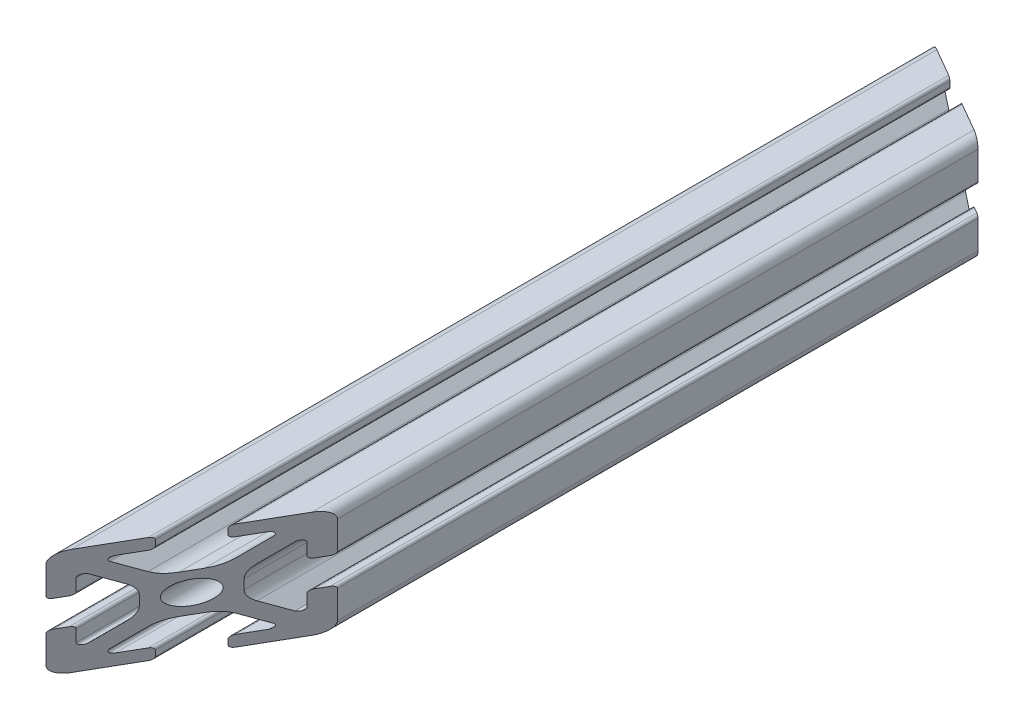
SolidWorks part; units mm, degrees
ref_plane "Front Plane" through (0, 0, 0) normal (0, 0, 1) x (1, 0, 0)
ref_plane "Top Plane" through (0, 0, 0) normal (0, 1, 0) x (1, 0, 0)
ref_plane "Right Plane" through (0, 0, 0) normal (1, 0, 0) x (0, 0, -1)
sketch "Sketch2" plane through (0, 0, 0) normal (0, 0, 1) x (1, 0, 0)
  line L0 (0, 10) -> (0, -10) construction
  line L1 (-10, 0) -> (10, 0) construction
  line L2 (2.5, -10) -> (10, -10)
  line L3 (10, -10) -> (10, -2.5)
  line L4 (2.5, -10) -> (2.5, -7.9246)
  line L5 (2.5, -7.9246) -> (6.4571, -7.9246)
  line L6 (6.4571, -7.9246) -> (2.1325, -3.6)
  line L7 (0, 0) -> (10, -10) construction
  line L8 (10, -2.5) -> (7.9246, -2.5)
  line L9 (7.9246, -2.5) -> (7.9246, -6.4571)
  line L10 (7.9246, -6.4571) -> (3.6, -2.1325)
  line L11 (5.7623, -4.2948) -> (4.2948, -5.7623) construction
  circle A0 centre (0, 0) radius 2.15
  arc A1 (5.25, -7.9246) -> (5.6036, -7.0711) centre (5.25, -7.4246) ccw construction
  point P8 (0, -3.6)
  point P16 (5.0286, -5.0286)
  dimension "Center Hole Diameter" = 4.3
  dimension "D3" = 0.5
  dimension "Rail Height" = 20
  dimension "Rail Width" = 20
  dimension "T-Slot Width" = 5
  dimension "Slot Depth" = 6.4
  dimension "Slot Inner Width" = 11.5
sketch "Sketch3" plane through (0, 0, 0) normal (1, 0, 0) x (0, 0, -1)
  line L0 (-100, -10) -> (100, -10) construction
  line L1 (-74.6, 0) -> (74.6, 0) construction
  line L2 (0, 10) -> (0, -10) construction
  line L3 (0, 10) -> (0, -10) construction
  point P6 (-74.6, 0)
  point P8 (74.6, 0)
  dimension "Length" = 200
  dimension "D1" = 25.4
sketch "Sketch4" plane through (0, 0, 0) normal (0, 0, 1) x (1, 0, 0)
  line L0 (3, -10) -> (8.25, -10)
  line L1 (2.5, -10) -> (10, -10) construction
  line L2 (2.5, -10) -> (2.5, -7.9246) construction
  line L3 (2.5, -7.9246) -> (6.4571, -7.9246) construction
  line L4 (2.5, -8.4246) -> (2.5, -9.5)
  line L5 (3, -7.9246) -> (5.25, -7.9246)
  line L6 (0, -3.6) -> (0.8898, -3.6)
  line L7 (6.4571, -7.9246) -> (2.1325, -3.6) construction
  line L8 (3.0112, -4.4787) -> (5.6036, -7.0711)
  line L9 (10, -10) -> (10, -2.5) construction
  line L10 (7.9246, -6.4571) -> (3.6, -2.1325) construction
  line L11 (7.9246, -2.5) -> (7.9246, -6.4571) construction
  line L12 (7.9246, -5.25) -> (7.9246, -3)
  line L13 (10, -2.5) -> (7.9246, -2.5) construction
  line L14 (8.4246, -2.5) -> (9.5, -2.5)
  line L15 (10, -3) -> (10, -8.25)
  line L16 (7.0711, -5.6036) -> (4.4787, -3.0112)
  line L17 (3.6, 0) -> (3.6, -0.8898)
  line L18 (-10, 0) -> (10, 0) construction
  line L19 (0, -3.6) -> (0, -2.15)
  line L20 (0, 10) -> (0, -10) construction
  line L21 (3.6, 0) -> (2.15, 0)
  arc A0 (2.5, -9.5) -> (3, -10) centre (3, -9.5) ccw
  arc A1 (5.25, -7.9246) -> (5.6036, -7.0711) centre (5.25, -7.4246) ccw construction
  arc A2 (2.5, -8.4246) -> (3, -7.9246) centre (3, -8.4246) cw
  arc A3 (5.25, -7.9246) -> (5.6036, -7.0711) centre (5.25, -7.4246) ccw
  arc A4 (0.8898, -3.6) -> (3.0112, -4.4787) centre (0.8898, -6.6) cw
  arc A5 (8.25, -10) -> (10, -8.25) centre (8.25, -8.25) ccw
  arc A6 (7.0711, -5.6036) -> (7.9246, -5.25) centre (7.4246, -5.25) ccw
  arc A7 (7.9246, -3) -> (8.4246, -2.5) centre (8.4246, -3) cw
  arc A8 (9.5, -2.5) -> (10, -3) centre (9.5, -3) cw
  arc A9 (4.4787, -3.0112) -> (3.6, -0.8898) centre (6.6, -0.8898) cw
  circle A10 centre (0, 0) radius 2.15 construction
  arc A11 (0, -2.15) -> (2.15, 0) centre (0, 0) ccw
  dimension "D1" = 1.75
  dimension "D2" = 3
extrude "Boss-Extrude1" add sketch "Sketch4" along normal mid plane 200
mirror "Mirror1" about plane through (0, 0, 0) normal (1, 0, 0) of bodies 134
mirror "Mirror2" about plane through (0, 0, 0) normal (0, 1, 0) of bodies 135
sketch "Sketch5" plane through (0, 10, 0) normal (0, 1, 0) x (1, 0, 0)
  line L0 (-10, -100) -> (62, 24.7077)
  line L4 (10, -100) -> (10, 100) construction
  line L7 (-11.6122, 67.2077) -> (62, 24.7077)
  line L8 (-11.6122, 67.2077) -> (-10, -100)
  dimension "D1" = 144
  dimension "D3" = 30
  dimension "D4" = 85
extrude "Cut-Extrude1" cut sketch "Sketch5" against normal through all flip side to cut
equation "\"D3@Sketch2\"=\"T-Slot Width@Sketch2\"*0.1"
equation "\"D1@Sketch4\"=\"D3@Sketch2\"*3.5"
equation "\"D2@Sketch4\"=\"D3@Sketch2\"*6"
equation "\"D1@Boss-Extrude1\"=\"Length@Sketch3\""
